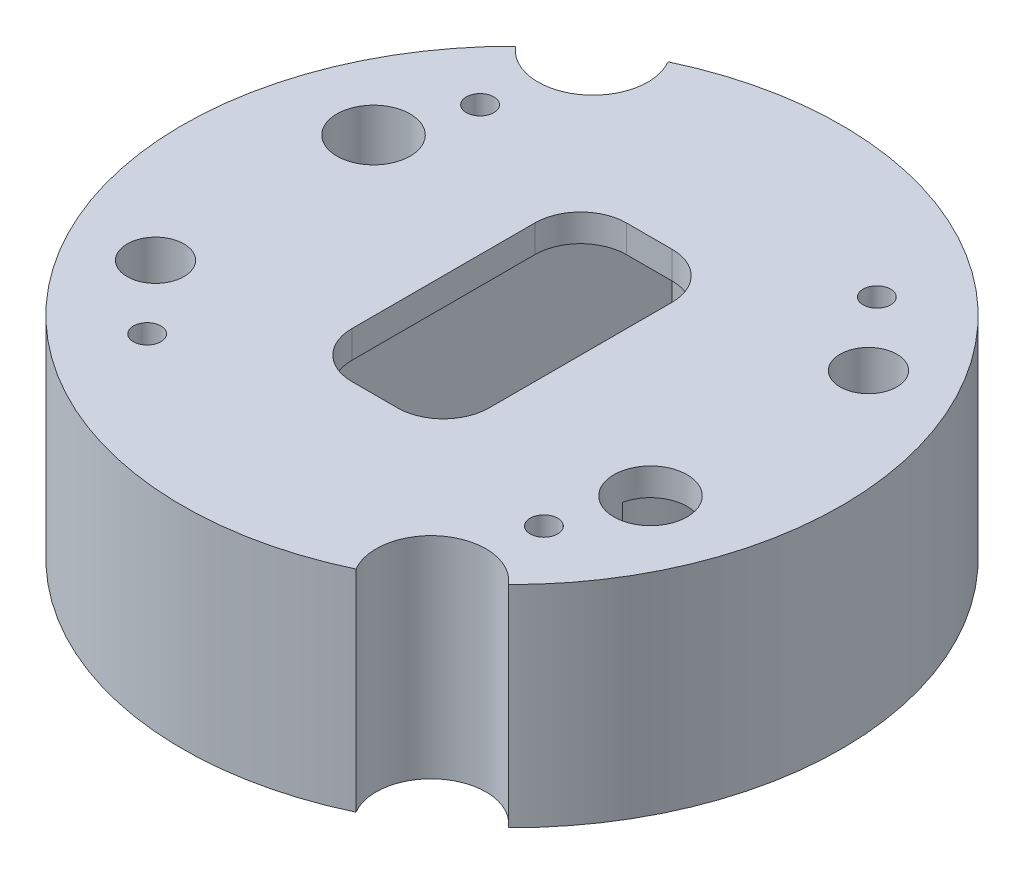
SolidWorks part; units mm, degrees
ref_plane "Front Plane" through (0, 0, 0) normal (0, 0, 1) x (1, 0, 0)
ref_plane "Top Plane" through (0, 0, 0) normal (0, 1, 0) x (1, 0, 0)
ref_plane "Right Plane" through (0, 0, 0) normal (1, 0, 0) x (0, 0, -1)
sketch "Sketch1" plane through (0, 0, 0) normal (0, 1, 0) x (1, 0, 0)
  line L0 (-13.25, 30.75) -> (13.25, -30.75) construction
  line L1 (-13.25, 30.75) -> (13.25, 30.75)
  line L2 (-13.25, 30.75) -> (-13.25, -30.75)
  line L3 (-13.25, -30.75) -> (13.25, -30.75)
  line L4 (13.25, 30.75) -> (13.25, -30.75)
  line L5 (-24.625, 0) -> (24.625, 0) construction
  line L6 (-34.125, 0) -> (-36, 0) construction
  line L7 (34.125, 0) -> (36, 0) construction
  line L8 (-15.125, 0) -> (-13.25, 0) construction
  circle A0 centre (0, 0) radius 36
  circle A3 centre (-24.625, 0) radius 9.5
  circle A4 centre (24.625, 0) radius 9.5
  point P5 (0, 0)
  point P12 (0, 0)
  dimension "D1" = 72
  dimension "D2" = 61.5
  dimension "D4" = 19
  dimension "D3" = 26.5
extrude "Boss-Extrude1" add sketch "Sketch1" along normal blind 20
sketch "Sketch4" plane through (0, 20, 0) normal (0, 1, 0) x (1, 0, 0)
  line L0 (-24.625, 9.5) -> (-24.625, 0) construction
  line L1 (-24.625, 0) -> (24.625, 0) construction
  line L2 (24.625, 0) -> (24.625, -9.5) construction
  line L3 (-24.625, 9.5) -> (-1.5428, 9.5) construction
  circle A0 centre (-24.625, 9.5) radius 4
  circle A1 centre (-24.625, 0) radius 9.5 construction
  circle A3 centre (24.625, -9.5) radius 4
  circle A5 centre (24.625, 0) radius 9.5 construction
  dimension "D1" = 8
extrude "Cut-Extrude6" cut sketch "Sketch4" against normal through all
sketch "Sketch5" plane through (0, 20, 0) normal (0, 1, 0) x (1, 0, 0)
  line L0 (0, 0) -> (20.0764, 0) construction
  line L1 (-18.1808, -21.667) -> (21.667, -18.1808) construction
  line L2 (-18.1808, -21.667) -> (-21.667, 18.1808) construction
  line L3 (-21.667, 18.1808) -> (18.1808, 21.667) construction
  line L4 (21.667, -18.1808) -> (18.1808, 21.667) construction
  line L5 (-18.1808, -21.667) -> (18.1808, 21.667) construction
  line L6 (-21.667, 18.1808) -> (21.667, -18.1808) construction
  circle A0 centre (-21.667, 18.1808) radius 1.5
  circle A1 centre (-18.1808, -21.667) radius 1.5
  circle A2 centre (21.667, -18.1808) radius 1.5
  circle A3 centre (18.1808, 21.667) radius 1.5
  circle A4 centre (-21.667, 18.1808) radius 2.3
  circle A5 centre (18.1808, 21.667) radius 2.3
  circle A6 centre (21.667, -18.1808) radius 2.3
  circle A7 centre (-18.1808, -21.667) radius 2.3
  point P0 (0, 0)
  dimension "D2" = 3
  dimension "D3" = 4.6
  dimension "D1" = 40
  dimension "D4" = 85
extrude "Cut-Extrude2" cut sketch "Sketch5" against normal blind 20 contours A0 | A3 | A1 | A2 region at (-21.667, 20, -18.1808) region at (-18.1808, 20, 21.667) region at (21.667, 20, 18.1808) region at (18.1808, 20, -21.667)
sketch "Sketch6" plane through (0, 20, 0) normal (0, 1, 0) x (1, 0, 0)
  line L0 (-24.6817, -14.25) -> (24.6817, 14.25) construction
  line L1 (0, 0) -> (24.909, 0) construction
  circle A0 centre (-24.6817, -14.25) radius 3.1
  circle A1 centre (24.6817, 14.25) radius 3.1
  point P4 (0, 0)
  dimension "D1" = 6.2
  dimension "D2" = 57
  dimension "D3" = 30
extrude "Cut-Extrude4" cut sketch "Sketch6" against normal through all both and the other way through all
sketch "Sketch7" plane through (0, 20, 0) normal (0, 1, 0) x (1, 0, 0)
  line L0 (-20.6488, 29.4895) -> (0, 0) construction
  line L1 (0, 0) -> (0, 21.7628) construction
  arc A0 (-25.2598, 25.6504) -> (-15.4641, 32.5094) centre (-20.6488, 29.4895) ccw
  circle A1 centre (0, 0) radius 36 construction
  arc A2 (-15.4641, 32.5094) -> (-25.2598, 25.6504) centre (0, 0) ccw
  dimension "D1" = 6
  dimension "D2" = 35
extrude "Cut-Extrude5" cut sketch "Sketch7" against normal through all both
sketch "Sketch9" plane through (0, 20, 0) normal (0, 1, 0) x (1, 0, 0)
  line L1 (-7.5, -15) -> (7.5, -15)
  line L2 (-7.5, -15) -> (-7.5, 15)
  line L3 (-7.5, 15) -> (7.5, 15)
  line L4 (-13.25, -30.75) -> (13.25, -30.75)
  line L5 (-13.25, 30.75) -> (-13.25, -30.75)
  line L6 (13.25, 30.75) -> (-13.25, 30.75)
  line L7 (13.25, -30.75) -> (13.25, 30.75)
  line L8 (-13.25, -30.75) -> (13.25, -30.75)
  line L9 (-13.25, 30.75) -> (-13.25, -30.75)
  line L10 (13.25, 30.75) -> (-13.25, 30.75)
  line L11 (13.25, -30.75) -> (13.25, 30.75)
  line L12 (7.5, -15) -> (7.5, 15)
  line L13 (-7.5, -15) -> (7.5, 15) construction
  line L14 (-7.5, 15) -> (7.5, -15) construction
  arc A0 (-28.5354, 8.6579) -> (-20.7146, 8.6579) centre (-24.625, 9.5) ccw
  circle A1 centre (21.667, -18.1808) radius 1.5
  arc A2 (20.7146, -8.6579) -> (28.5354, -8.6579) centre (24.625, -9.5) ccw
  arc A3 (28.5354, -8.6579) -> (20.7146, -8.6579) centre (24.625, 0) ccw
  arc A4 (20.7146, -8.6579) -> (28.5354, -8.6579) centre (24.625, -9.5) ccw
  arc A5 (28.5354, -8.6579) -> (20.7146, -8.6579) centre (24.625, 0) ccw
  arc A6 (-20.7146, 8.6579) -> (-28.5354, 8.6579) centre (-24.625, 9.5) ccw
  arc A7 (-28.5354, 8.6579) -> (-20.7146, 8.6579) centre (-24.625, 0) ccw
  arc A8 (-20.7146, 8.6579) -> (-28.5354, 8.6579) centre (-24.625, 9.5) ccw
  arc A9 (-28.5354, 8.6579) -> (-20.7146, 8.6579) centre (-24.625, 0) ccw
  circle A10 centre (21.667, -18.1808) radius 1.5
  circle A11 centre (-18.1808, -21.667) radius 1.5
  circle A12 centre (-18.1808, -21.667) radius 1.5
  circle A13 centre (18.1808, 21.667) radius 1.5
  circle A14 centre (18.1808, 21.667) radius 1.5
  circle A15 centre (-21.667, 18.1808) radius 1.5
  circle A16 centre (-21.667, 18.1808) radius 1.5
  circle A17 centre (24.6817, 14.25) radius 3.1
  circle A18 centre (24.6817, 14.25) radius 3.1
  circle A19 centre (-24.6817, -14.25) radius 3.1
  circle A20 centre (-24.6817, -14.25) radius 3.1
  arc A21 (28.5354, -8.6579) -> (20.7146, -8.6579) centre (24.625, -9.5) ccw
  arc A22 (-25.2598, 25.6504) -> (-15.4641, 32.5094) centre (-20.6488, 29.4895) ccw
  arc A23 (-25.2598, 25.6504) -> (-15.4641, 32.5094) centre (0, 0) ccw
  arc A24 (-25.2598, 25.6504) -> (-15.4641, 32.5094) centre (-20.6488, 29.4895) ccw
  arc A25 (-25.2598, 25.6504) -> (-15.4641, 32.5094) centre (0, 0) ccw
  arc M17 (-15.4641, 32.5094) -> (-25.2598, 25.6504) centre (-20.6488, 29.4895) cw
  arc M18 (-25.2598, 25.6504) -> (-15.4641, 32.5094) centre (0, 0) ccw
  circle M19 centre (-24.6817, -14.25) radius 3.1
  circle M20 centre (24.6817, 14.25) radius 3.1
  circle M21 centre (-21.667, 18.1808) radius 1.5
  circle M22 centre (18.1808, 21.667) radius 1.5
  circle M23 centre (-18.1808, -21.667) radius 1.5
  circle M24 centre (21.667, -18.1808) radius 1.5
  arc M25 (-28.5354, 8.6579) -> (-20.7146, 8.6579) centre (-24.625, 9.5) cw
  arc M26 (-20.7146, 8.6579) -> (-28.5354, 8.6579) centre (-24.625, 0) cw
  arc M27 (28.5354, -8.6579) -> (20.7146, -8.6579) centre (24.625, -9.5) cw
  arc M28 (20.7146, -8.6579) -> (28.5354, -8.6579) centre (24.625, 0) cw
  line M29 (13.25, -30.75) -> (-13.25, -30.75)
  line M30 (-13.25, -30.75) -> (-13.25, 30.75)
  line M31 (-13.25, 30.75) -> (13.25, 30.75)
  line M32 (13.25, 30.75) -> (13.25, -30.75)
  dimension "D11" = 15
  dimension "D12" = 30
  dimension "D1" = 0
  dimension "D2" = 0
  dimension "D3" = 0
  dimension "D4" = 0
  dimension "D5" = 0
  dimension "D6" = 0
  dimension "D7" = 0
  dimension "D8" = 0
  dimension "D9" = 0
  dimension "D10" = 0
extrude "Boss-Extrude2" add sketch "Sketch9" along normal blind 3 contours M18 M17 M19 M21 M23 M26 M25 M28 M27 M32 M29 M30 M31 M24 M22 M20 | A0 M26 | A21 M28 | M29 M32 M31 M30 region at (-12.5803, 20, 0) region at (-24.625, 20, 0.6723) region at (24.625, 20, -0.6723) region at (-16.6233, 20, -23.7405)
fillet "Fillet1" radius 5 4 edges at (7.5, 21.5, 15) (-7.5, 21.5, 15) (-7.5, 21.5, -15) (7.5, 21.5, -15)
pattern_circular "CirPattern1" count 2 over 360 about axis through (0, 23, 0) along (0, 1, 0) of face at (-18.7846, 11.5, -26.8272)
